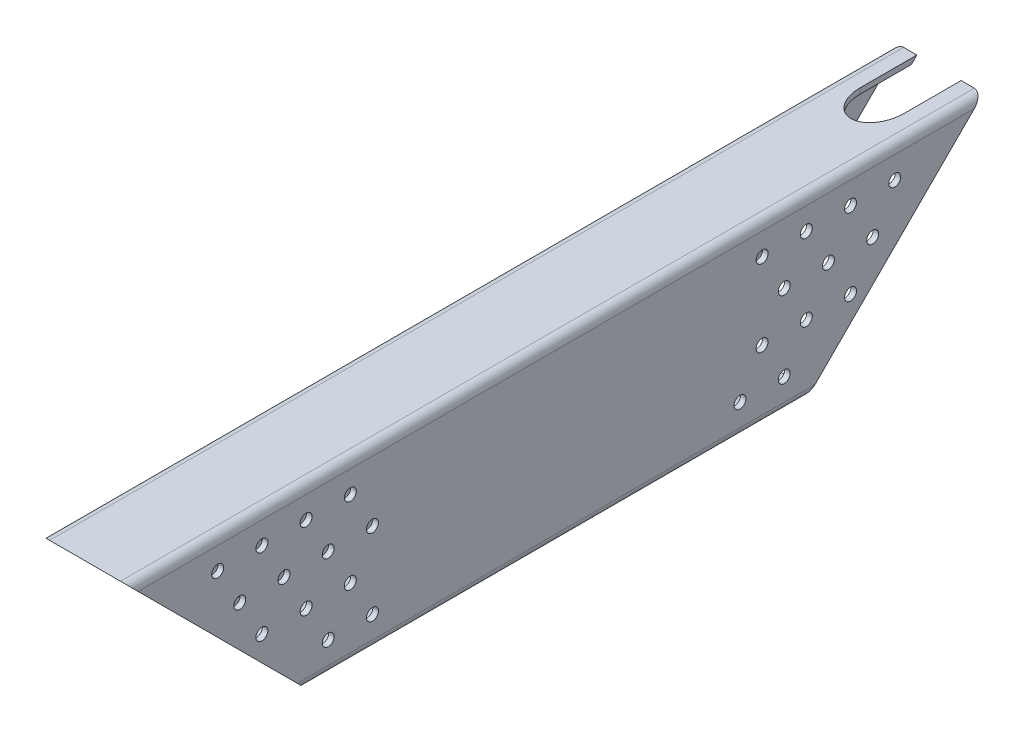
SolidWorks part; units mm, degrees
material "6061-T6 (SS)"
ref_plane "Front" through (0, 0, 0) normal (0, 0, 1) x (1, 0, 0)
ref_plane "Top" through (0, 0, 0) normal (0, 1, 0) x (1, 0, 0)
ref_plane "Right" through (0, 0, 0) normal (1, 0, 0) x (0, 0, -1)
sketch "Sketch3" plane through (0, 0, 0) normal (1, 0, 0) x (0, 0, -1)
  line L0 (-50.8, -25.4) -> (-194.4841, -25.4)
  line L1 (-194.4841, -25.4) -> (-245.2841, 25.4)
  line L2 (-245.2841, 25.4) -> (0, 25.4)
  line L3 (0, 25.4) -> (-50.8, -25.4)
  point P8 (-25.4, 0)
  dimension "D1" = 50.8
  dimension "D2" = 101.6
  dimension "D3" = 45
sketch "Sketch1" plane through (0, 0, 0) normal (0, 0, 1) x (1, 0, 0)
  line L1 (-10.16, -25.4) -> (10.16, -25.4)
  line L2 (-12.7, -22.86) -> (-12.7, 22.86)
  line L3 (-10.16, 25.4) -> (10.16, 25.4)
  line L4 (12.7, -22.86) -> (12.7, 22.86)
  line L5 (-12.7, -25.4) -> (12.7, 25.4) construction
  line L6 (-12.7, 25.4) -> (12.7, -25.4) construction
  arc A0 (-10.16, -25.4) -> (-12.7, -22.86) centre (-10.16, -22.86) cw
  arc A1 (10.16, -25.4) -> (12.7, -22.86) centre (10.16, -22.86) ccw
  arc A2 (10.16, 25.4) -> (12.7, 22.86) centre (10.16, 22.86) cw
  arc A3 (-12.7, 22.86) -> (-10.16, 25.4) centre (-10.16, 22.86) cw
  point P0 (0, 0)
  dimension "D3" = 2.54
  dimension "D1" = 25.4
  dimension "D2" = 50.8
extrude "Extrude-Thin1" add sketch "Sketch1" along normal up to vertex (245.2841 mm away) thin up to point (0, 25.4, 245.2841) thin type one direction reverse wall 1.5875
sketch "Sketch2" plane through (12.7, 0, 0) normal (1, 0, 0) x (0, 0, -1)
  line L0 (-245.2841, 25.4) -> (-194.4841, -25.4)
  line L1 (-245.2841, -25.4) -> (0, -25.4) construction
  line L2 (-194.4841, -25.4) -> (-245.2841, -25.4)
  line L3 (-245.2841, -25.4) -> (-245.2841, 25.4)
  line L4 (0, 25.4) -> (-50.8, -25.4)
  line L5 (-50.8, -25.4) -> (0, -25.4)
  line L6 (0, -25.4) -> (0, 25.4)
  line L7 (0, 25.4) -> (-50.8, -25.4) construction
  line L8 (-194.4841, -25.4) -> (-245.2841, 25.4) construction
extrude "Cut-Extrude1" cut sketch "Sketch2" against normal through all
sketch "Sketch4" plane through (0, 12.7, 12.7) normal (0, -0.7071, -0.7071) x (1, 0, 0)
  circle A0 centre (0, -22.3185) radius 6.35
  circle A1 centre (0, -6.4435) radius 6.35
  circle A2 centre (0, -38.1935) radius 6.35
  dimension "D1" = 12.7
extrude "Cut-Extrude2" cut sketch "Sketch4" against normal through all
sketch "Sketch5" plane through (0, 25.4, 0) normal (0, 1, 0) x (1, 0, 0)
  line L0 (-6.35, -16.2876) -> (-6.35, 0)
  line L1 (-6.35, 0) -> (6.35, 0)
  line L2 (6.35, 0) -> (6.35, -16.2876)
  line L3 (-4.6185, 0) -> (-10.16, 0) construction
  ellipse E1 centre (0, -16.2876) end of major axis (0, -7.3073) minor radius 6.35 construction
  ellipse E3 centre (0, -16.2876) end of major axis (0, -7.3073) minor radius 6.35 (-6.35, -16.2876) -> (6.35, -16.2876) ccw
extrude "Cut-Extrude3" cut sketch "Sketch5" against normal through all
hole_wizard "1/8 (0.135) Diameter Hole1" positions "Sketch6" profile "Sketch7" hole size "1/8" standard "ANSI Inch" end condition through all
sketch "Sketch6" plane through (-12.7, 0, 0) normal (-1, 0, 0) x (0, 0, 1)
  point P78 (63.5, 16.4978)
  point P81 (57.15, 5.4993)
  point P84 (50.8, 16.4978)
  point P87 (38.1, 16.4978)
  point P90 (25.4, 16.4978)
  point P93 (31.75, 5.4993)
  point P96 (44.45, 5.4993)
  point P99 (38.1, -5.4993)
  point P102 (50.8, -5.4993)
  point P105 (63.5, -5.4993)
  point P108 (57.15, -16.4978)
  point P111 (69.85, -16.4978)
  point P116 (181.7841, 16.4978)
  point P119 (194.4841, 16.4978)
  point P122 (207.1841, 16.4978)
  point P125 (219.8841, 16.4978)
  point P128 (213.5341, 5.4993)
  point P131 (200.8341, 5.4993)
  point P134 (188.1341, 5.4993)
  point P137 (175.4341, 5.4993)
  point P140 (181.7841, -5.4993)
  point P143 (194.4841, -5.4993)
  point P146 (207.1841, -5.4993)
  point P149 (188.1341, -16.4978)
  point P152 (175.4341, -16.4978)
sketch "Sketch7" plane through (-12.7, 16.4978, 63.5) normal (0, 1, 0) x (0, 0, 1)
  line L0 (0, 0) -> (0, 25.4)
  line L1 (0, 25.4) -> (1.7145, 25.4)
  line L2 (1.7145, 25.4) -> (1.7145, 0)
  line L5 (1.7145, 0) -> (0, 0)
  line L11 (0, -6.35) -> (0, 107.95) construction
  dimension "Thru Hole Dia." = 3.429
  dimension "Thru Hole Depth" = 25.4
